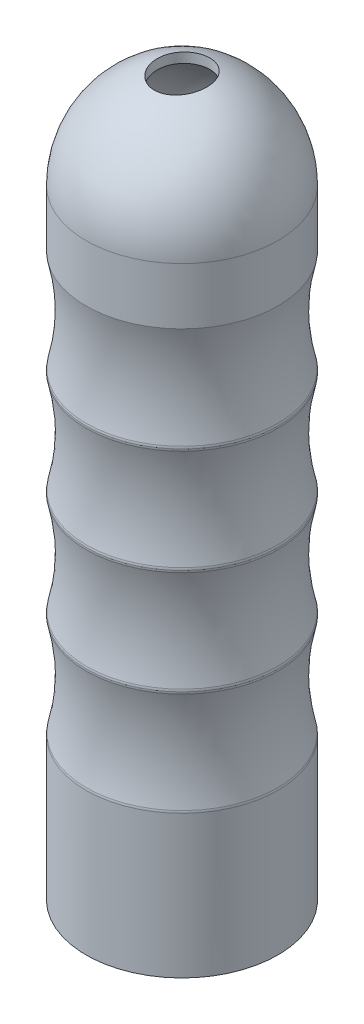
SolidWorks part; units mm, degrees
ref_plane "Alzado" through (0, 0, 0) normal (0, 0, 1) x (1, 0, 0)
ref_plane "Planta" through (0, 0, 0) normal (0, 1, 0) x (1, 0, 0)
ref_plane "Vista lateral" through (0, 0, 0) normal (1, 0, 0) x (0, 0, -1)
sketch "Croquis2" plane through (0, 0, 0) normal (0, 0, 1) x (1, 0, 0)
  line L0 (-15.5, 100) -> (-15.5, 90.8661)
  line L1 (55, 0) -> (-55, 0) construction
  line L2 (0, 0) -> (0, 122.3764) construction
  line L3 (-14, 100) -> (-14, 91.0476)
  line L4 (-15.5, 0) -> (-14, 0)
  line L5 (0, -55) -> (0, 55) construction
  line L6 (0, 115) -> (0, 116.4964)
  line L7 (0, 116.4964) -> (-0.1033, 116.4964)
  line L8 (-14, 23.0476) -> (-14, 0)
  line L9 (-15.5, 74.2292) -> (-15.5, 73.8661)
  line L10 (-15.5, 57.2292) -> (-15.5, 56.8661)
  line L11 (-15.5, 40.2292) -> (-15.5, 39.8661)
  line L12 (-15.5, 23.2292) -> (-15.5, 0)
  arc A0 (-14, 100) -> (0, 115) centre (1.0357, 100) cw
  arc A1 (-15.5, 100) -> (-0.1033, 116.4964) centre (1.0357, 100) cw
  arc A2 (-14, 91.0476) -> (-14, 74.0476) centre (-48.9821, 82.5476) cw
  arc A3 (-15.5, 90.8661) -> (-15.5, 74.2292) centre (-48.9821, 82.5476) cw
  arc A4 (-15.4576, 90.6935) -> (-15.4576, 74.4018) centre (-48.9821, 82.5476) cw construction
  arc A5 (-14, 74.0476) -> (-14, 57.0476) centre (-48.9821, 65.5476) cw
  arc A6 (-15.5, 73.8661) -> (-15.5, 57.2292) centre (-48.9821, 65.5476) cw
  arc A7 (-15.4576, 73.6935) -> (-15.4576, 57.4018) centre (-48.9821, 65.5476) cw construction
  arc A8 (-14, 57.0476) -> (-14, 40.0476) centre (-48.9821, 48.5476) cw
  arc A9 (-15.5, 56.8661) -> (-15.5, 40.2292) centre (-48.9821, 48.5476) cw
  arc A10 (-15.4576, 56.6935) -> (-15.4576, 40.4018) centre (-48.9821, 48.5476) cw construction
  arc A11 (-14, 40.0476) -> (-14, 23.0476) centre (-48.9821, 31.5476) cw
  arc A12 (-15.5, 39.8661) -> (-15.5, 23.2292) centre (-48.9821, 31.5476) cw
  arc A13 (-15.4576, 39.6935) -> (-15.4576, 23.4018) centre (-48.9821, 31.5476) cw construction
  point P40 (0, 0)
  dimension "D2" = 36
  dimension "D3" = 36
  dimension "D8" = 36
  dimension "D11" = 36
  dimension "D1" = 1.5
  dimension "D4" = 1.5
  dimension "D6" = 17
  dimension "D7" = 17
  dimension "D9" = 17
  dimension "D12" = 17
  dimension "D5" = 1.5
  dimension "D10" = 1.5
  dimension "D13" = 1.5
revolve "Revolución2" add sketch "Croquis2" angle 360 about L2
sketch "Croquis3" plane through (0, 0, 0) normal (0, 1, 0) x (1, 0, 0)
  ellipse E0 centre (0, 0) end of major axis (0, -4.5) minor radius 4
  point P1 (0, 0)
  point P7 (0, 0)
  point P8 (0, 0)
  point P9 (0, 0)
  point P10 (0, 0)
  point P11 (0, 0)
  point P12 (0, 0)
  point P14 (0, 0)
  dimension "D1" = 0
  dimension "D2" = 9
  dimension "D3" = 8
extrude "Cortar-Extruir6" cut sketch "Croquis3" along normal blind 143 from offset 40
fillet "Redondeo5" radius 1.5 7 edges at (0, 56.8661, -15.5) (0, 57.2292, -15.5) (0, 73.8661, -15.5) (0, 74.2292, -15.5) (0, 40.2292, -15.5) (0, 39.8661, -15.5) (0, 23.2292, -15.5)
